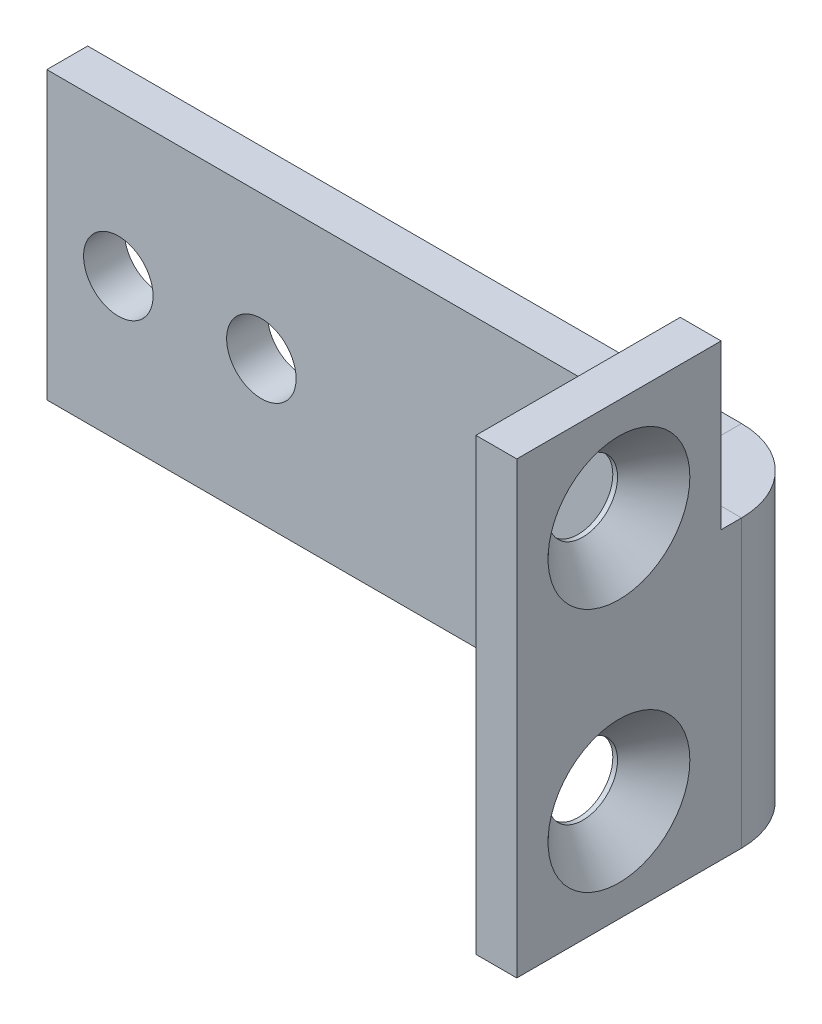
SolidWorks part; units mm, degrees
note: The reader was unsure of these and kept them because the rebuilt part matched: flange length of "Kante-Lasche1".
ref_plane "Ebene vorne" through (0, 0, 0) normal (0, 0, 1) x (1, 0, 0)
ref_plane "Ebene oben" through (0, 0, 0) normal (0, 1, 0) x (1, 0, 0)
ref_plane "Ebene rechts" through (0, 0, 0) normal (1, 0, 0) x (0, 0, -1)
sketch "Skizze1" plane through (0, 0, 0) normal (0, 0, 1) x (1, 0, 0)
  line L1 (0, 0) -> (34, 0)
  line L2 (0, 0) -> (0, 14)
  line L3 (0, 14) -> (34, 14)
  line L4 (34, 0) -> (34, 14)
  dimension "D1" = 34
  dimension "D2" = 14
base flange "Basis-Blech1" sketch "Skizze1" thickness 2 reverse thickness direction no parameters "D1"=2
edge flange "Kante-Lasche1" sketch "Skizze9" flange angle 90 flange length 13 flange position material outside bend radius 2 thickness 2 relief rectangular parameters "D1"=0.7366, "D6"=10
sketch "Skizze9" plane through (34, 0, 0) normal (1, 0, 0) x (0, 1, 0)
  line L0 (0, 0) -> (14, 0) construction
  line L1 (0, 0) -> (14, 0)
  line L2 (0, 0) -> (0, 13)
  line L3 (14, 3) -> (22, 3)
  line L4 (14, 3) -> (14, 0)
  line L5 (22, 3) -> (22, 13)
  line L6 (22, 13) -> (0, 13)
  dimension "D1" = 13
  dimension "D2" = 22
  dimension "D3" = 3
bend "Kantenbiegung1" bend radius 2 bend angle 90 parameters "D5"=1
sketch "Skizze10" plane through (0, 0, 0) normal (0, 0, 1) x (1, 0, 0)
  line L0 (0, 7) -> (32, 7) construction
  line L1 (0, 14) -> (0, 0) construction
  line L2 (32, 14) -> (32, 0) construction
  circle A0 centre (3.5, 7) radius 1.7
  circle A1 centre (10.5, 7) radius 1.7
  dimension "D1" = 3.4
  dimension "D2" = 3.5
  dimension "D3" = 10.5
extrude "Schnitt-Linear austragen1" cut sketch "Skizze10" against normal through all normal cut yes
hole_wizard "Formsenkung für M3 Senkschraube mit Innensechskant1" positions "Skizze12" profile "Skizze11" countersink size "M3" standard "DIN" end condition through all
sketch "Skizze12" plane through (36, 0, 0) normal (1, 0, 0) x (0, 0, -1)
  line L0 (-8, 5) -> (-8, 17) construction
  line L1 (-8, 17) -> (-8, 22) construction
  line L4 (-8, 5) -> (-8, 0) construction
  line L5 (-13, 0) -> (-2, 0) construction
  line L7 (-3, 22) -> (-13, 22) construction
  line L8 (-8, 5) -> (-13, 5) construction
  line L9 (-13, 22) -> (-13, 0) construction
  point P0 (-8, 5)
  point P2 (-8, 17)
  dimension "D1" = 5
sketch "Skizze11" plane through (36, 5, 8) normal (0, 1, 0) x (0, 0, -1)
  line L0 (0, 0) -> (0, 36)
  line L1 (0, 36) -> (1.7, 36)
  line L2 (1.7, 36) -> (1.7, 1.77)
  line L3 (1.7, 1.77) -> (3.47, 0)
  line L5 (3.47, 0) -> (0, 0)
  line L6 (-1.7, 1.77) -> (-3.47, 0) construction
  line L11 (0, -6.35) -> (0, 107.95) construction
  dimension "Bohrerdurchmesser" = 3.4
  dimension "Bohrungstiefe" = 36
  dimension "Senkdurchmesser (Oben)" = 6.94
  dimension "Senkwinkel (Oben)" = 90
sketch "Biegung-Linien1" plane through (0, 0, 0) normal (0, 1, 0) x (1, 0, 0)
sketch "Rahmen1" plane through (0, 0, 0) normal (0, 1, 0) x (1, 0, 0)
sheet metal parameters "Blech(2)" thickness 2 parameters "D1"=0.7366
flat pattern "Abwicklung(2)"
sketch "Biegung-Linien2" plane through (0, 0, 0) normal (0, 1, 0) x (1, 0, 0)
sketch "Rahmen2" plane through (0, 0, 0) normal (0, 1, 0) x (1, 0, 0)
sheet metal parameters "Blech(3)" thickness 2 parameters "D1"=0.7366
flat pattern "Abwicklung(2)"
sketch "Biegung-Linien2" plane through (0, 0, 0) normal (0, 1, 0) x (1, 0, 0)
sketch "Rahmen2" plane through (0, 0, 0) normal (0, 1, 0) x (1, 0, 0)
bend of the flat pattern "Abwickeln-<Kantenbiegung1>1"
sheet metal parameters "Blech(4)" thickness 2 parameters "D1"=0.7366
flat pattern "Abwicklung(2)"
sketch "Biegung-Linien2" plane through (0, 0, 0) normal (0, 1, 0) x (1, 0, 0)
sketch "Rahmen2" plane through (0, 0, 0) normal (0, 1, 0) x (1, 0, 0)
bend of the flat pattern "Abwickeln-<Kantenbiegung1>1"
sheet metal parameters "Blech(5)" thickness 2 parameters "D1"=0.7366
flat pattern "Abwicklung(2)"
sketch "Biegung-Linien2" plane through (0, 0, 0) normal (0, 0, 1) x (1, 0, 0)
  line L0 (34.3562, 0) -> (34.3562, 14) construction
  line L1 (34.3562, 0) -> (34.3562, 14) construction
sketch3d "Rahmen2"
  line L0 (0, 0, 0) -> (47.7124, 0, 0) construction
  line L1 (0, 22, 0) -> (47.7124, 22, 0) construction
  line L2 (0, 0, 0) -> (0, 22, 0) construction
  line L3 (47.7124, 0, 0) -> (47.7124, 22, 0) construction
bend of the flat pattern "Abwickeln-<Kantenbiegung1>1"
